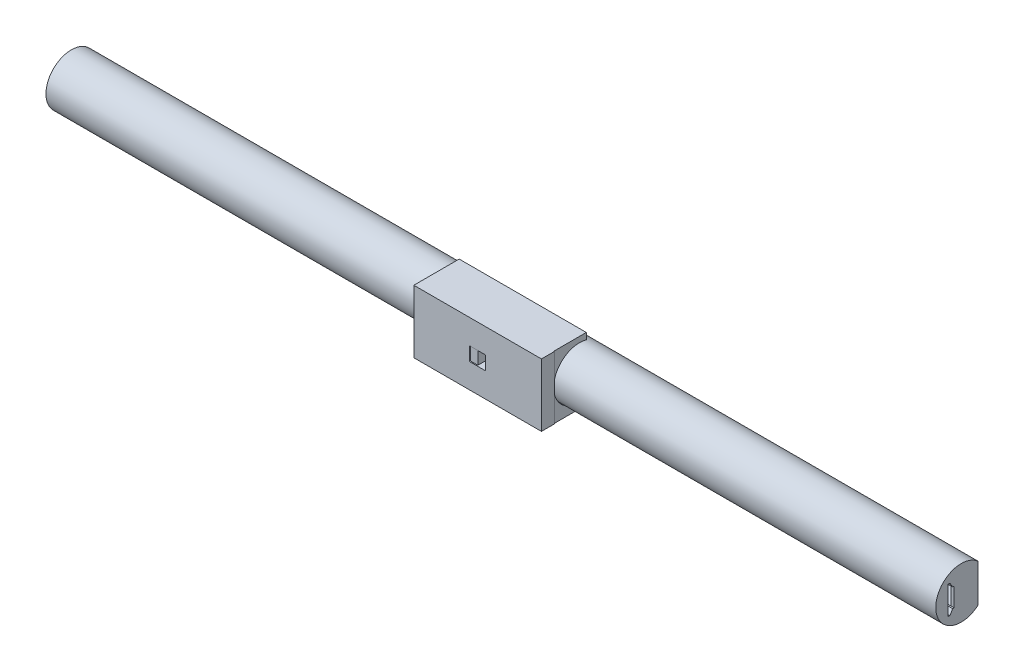
SolidWorks part; units mm, degrees
ref_plane "Front Plane" through (0, 0, 0) normal (0, 0, 1) x (1, 0, 0)
ref_plane "Top Plane" through (0, 0, 0) normal (0, 1, 0) x (1, 0, 0)
ref_plane "Right Plane" through (0, 0, 0) normal (1, 0, 0) x (0, 0, -1)
sketch "NewBarProfile" plane through (0, 0, 0) normal (1, 0, 0) x (0, 1, 0)
  line L0 (7.5, -6.6144) -> (-7.5, -6.6144) construction
  line L1 (-7.5, -6.6144) -> (-6.3, -6.6144)
  line L2 (-6.3, -6.6144) -> (-6.3, 1.2617)
  line L3 (-6.3, 1.2617) -> (0, 4.899) construction
  line L4 (5, 4.899) -> (-5, 4.899) construction
  line L5 (0, -14.4444) -> (0, 14.4444) construction
  line L6 (-5.5, 5.199) -> (5.5, 5.199)
  line L7 (-6.3, 1.2617) -> (-3.7026, 2.7613)
  line L8 (0, 0) -> (-7.1429, 6.9985) construction
  line L9 (-5.5, 4.399) -> (-3.7026, 3.3613)
  line L10 (-5.5, 5.199) -> (-5.5, 4.399)
  line L11 (-3.7026, 3.3613) -> (-3.7026, 2.7613)
  line L12 (7.5, -6.6144) -> (6.3, -6.6144)
  line L13 (3.7026, 3.3613) -> (3.7026, 2.7613)
  line L14 (5.5, 5.199) -> (5.5, 4.399)
  line L15 (5.5, 4.399) -> (3.7026, 3.3613)
  line L16 (6.3, 1.2617) -> (3.7026, 2.7613)
  line L17 (6.3, -6.6144) -> (6.3, 1.2617)
  line L18 (0, -11) -> (0, 11) construction
  circle A0 centre (0, 0) radius 10 construction
  arc A1 (-7.5, -6.6144) -> (7.5, -6.6144) centre (0, 0) cw
  arc A2 (-6.6144, -7.5) -> (-6.6144, 7.5) centre (0, 0) ccw construction
  point P11 (0, 4.899)
  point P14 (0, 0)
  point P17 (-3.2212, 3.0769)
  point P18 (-3.421, 3.3519)
  point P19 (-3.0403, 2.9789)
  point P22 (-3.0403, 2.9789)
  point P30 (5.6596, 5.199)
sketch "Sketch5" plane through (0, 0, 3.7) normal (1, 0, 0) x (0, 1, 0)
  line L0 (0, -16.5814) -> (0, 9.1814) construction
  line L5 (-7.5, -2.6947) -> (-6.4, -4.6) construction
  line L6 (7.5, -2.6947) -> (6.4, -4.6) construction
  line L7 (5.3668, 1) -> (7.5, -2.6947) construction
  line L8 (-5.3668, 1) -> (5.3668, 1) construction
  line L9 (-5.3668, 1) -> (-7.5, -2.6947) construction
  line L10 (7.7309, -2.6947) -> (6.5732, -4.7)
  line L11 (5.4823, 1.2) -> (7.7309, -2.6947)
  line L12 (-5.4823, 1.2) -> (5.4823, 1.2)
  line L13 (-5.4823, 1.2) -> (-7.7309, -2.6947)
  line L14 (-7.7309, -2.6947) -> (-6.5732, -4.7)
  line L15 (-6.5732, -4.7) -> (6.5732, -4.7)
  line L17 (0, -9.7207) -> (0, 9.7207) construction
  line L18 (-6.9, -10.9381) -> (6.9, -10.9381)
  line L19 (0, -10.9381) -> (0, -3.7) construction
  circle A0 centre (0, -3.7) radius 10 construction
  arc A1 (-6.9, -10.9381) -> (6.9, -10.9381) centre (0, -3.7) cw
  point P18 (0, -13.7)
sketch "Sketch8" plane through (0, 0, 3.7) normal (0, -1, 0) x (1, 0, 0)
  line L2 (0, -9.7207) -> (-145, -9.7207)
  line L3 (0, -9.9381) -> (-145, -9.9381)
  line L4 (0, -10.9381) -> (-150, -10.9381)
  point P0 (0, -9.7207)
  point P3 (0, -10.9381)
sketch "Sketch9" plane through (0, 0, 3.7) normal (1, 0, 0) x (0, 1, 0)
  line L0 (-6.9, -10.9381) -> (6.9, -10.9381) construction
  line L3 (-6.9, -10.9381) -> (6.9, -10.9381) construction
  line L4 (-6.4874, -9.9381) -> (6.4874, -9.9381)
  line L5 (-6.4017, -9.7381) -> (6.4017, -9.7381)
  arc A3 (6.9, -10.9381) -> (-6.9, -10.9381) centre (0, -3.7) ccw construction
  arc A4 (6.4874, -9.9381) -> (-6.4874, -9.9381) centre (0, -3.7) ccw
  arc A5 (6.4017, -9.7381) -> (-6.4017, -9.7381) centre (0, -3.7) ccw
sketch "Sketch1" plane through (0, 0, 0) normal (1, 0, 0) x (0, 0, -1)
  line L63 (-5.199, 5.5) -> (-4.399, 5.5)
  line L64 (-4.399, 5.5) -> (-3.3613, 3.7026)
  line L65 (-3.3613, 3.7026) -> (-2.7613, 3.7026)
  line L66 (-2.7613, 3.7026) -> (-1.2617, 6.3)
  line L67 (-1.2617, 6.3) -> (6.6144, 6.3)
  line L68 (6.6144, 6.3) -> (6.6144, 7.5)
  line L69 (6.6144, -7.5) -> (6.6144, -6.3)
  line L70 (6.6144, -6.3) -> (-1.2617, -6.3)
  line L71 (-1.2617, -6.3) -> (-2.7613, -3.7026)
  line L72 (-2.7613, -3.7026) -> (-3.3613, -3.7026)
  line L73 (-3.3613, -3.7026) -> (-4.399, -5.5)
  line L74 (-4.399, -5.5) -> (-5.199, -5.5)
  line L75 (-5.199, -5.5) -> (-5.199, 5.5)
  line L76 (-5.199, 5.5) -> (-4.399, 5.5)
  line L77 (-4.399, 5.5) -> (-3.3613, 3.7026)
  line L78 (-3.3613, 3.7026) -> (-2.7613, 3.7026)
  line L79 (-2.7613, 3.7026) -> (-1.2617, 6.3)
  line L80 (-1.2617, 6.3) -> (6.6144, 6.3)
  line L81 (6.6144, 6.3) -> (6.6144, 7.5)
  line L82 (6.6144, -7.5) -> (6.6144, -6.3)
  line L83 (6.6144, -6.3) -> (-1.2617, -6.3)
  line L84 (-1.2617, -6.3) -> (-2.7613, -3.7026)
  line L85 (-2.7613, -3.7026) -> (-3.3613, -3.7026)
  line L86 (-3.3613, -3.7026) -> (-4.399, -5.5)
  line L87 (-4.399, -5.5) -> (-5.199, -5.5)
  line L88 (-5.199, -5.5) -> (-5.199, 5.5)
  arc A9 (6.6144, 7.5) -> (6.6144, -7.5) centre (0, 0) ccw
  arc A10 (6.6144, 7.5) -> (6.6144, -7.5) centre (0, 0) ccw
  dimension "D1" = 0
extrude "Bar" add sketch "Sketch1" against normal mid plane 350
sketch "Sketch13" plane through (0, 0, -6.6144) normal (0, 0, -1) x (-1, 0, 0)
  line L0 (175, 7.5) -> (175, -7.5)
  line L1 (175, -7.5) -> (173.8, -7.5)
  line L2 (175, -7.5) -> (-175, -7.5) construction
  line L3 (173.8, -7.5) -> (173.8, 7.5)
  line L4 (175, 7.5) -> (-175, 7.5) construction
  line L5 (173.8, 7.5) -> (175, 7.5)
  line L6 (125.4, 7.5) -> (124.6, 7.5)
  line L7 (124.6, 7.5) -> (124.6, -7.5)
  line L8 (124.6, -7.5) -> (125.4, -7.5)
  line L9 (125.4, -7.5) -> (125.4, 7.5)
  line L10 (125, 7.5) -> (125, -7.5) construction
  line L11 (75.4, -7.5) -> (75.4, 7.5)
  line L12 (75.4, 7.5) -> (74.6, 7.5)
  line L13 (74.6, 7.5) -> (74.6, -7.5)
  line L14 (74.6, -7.5) -> (75.4, -7.5)
  line L15 (25.4, -7.5) -> (25.4, 7.5)
  line L16 (25.4, 7.5) -> (24.6, 7.5)
  line L17 (24.6, 7.5) -> (24.6, -7.5)
  line L18 (24.6, -7.5) -> (25.4, -7.5)
  line L19 (-24.6, -7.5) -> (-24.6, 7.5)
  line L20 (-24.6, 7.5) -> (-25.4, 7.5)
  line L21 (-25.4, 7.5) -> (-25.4, -7.5)
  line L22 (-25.4, -7.5) -> (-24.6, -7.5)
  line L23 (-74.6, -7.5) -> (-74.6, 7.5)
  line L24 (-74.6, 7.5) -> (-75.4, 7.5)
  line L25 (-75.4, 7.5) -> (-75.4, -7.5)
  line L26 (-75.4, -7.5) -> (-74.6, -7.5)
  line L27 (-124.6, -7.5) -> (-124.6, 7.5)
  line L28 (-124.6, 7.5) -> (-125.4, 7.5)
  line L29 (-125.4, 7.5) -> (-125.4, -7.5)
  line L30 (-125.4, -7.5) -> (-124.6, -7.5)
  line L31 (0, -34.8434) -> (0, 34.8434) construction
  line L32 (-173.8, -7.5) -> (-173.8, 7.5)
  line L33 (-175, -7.5) -> (-173.8, -7.5)
  line L34 (-175, 7.5) -> (-175, -7.5)
  line L35 (-173.8, 7.5) -> (-175, 7.5)
  point P40 (0, 0)
  dimension "D1" = 1.2
  dimension "D2" = 0.8
  dimension "D3" = 50
  dimension "D5" = 50
  dimension "D4" = 6
extrude "Boss-Extrude1" add sketch "Sketch13" against normal up to vertex (9.3756 mm away) up to point (175, 3.7026, 2.7613)
sketch "Sketch14" plane through (0, 0, 0) normal (0, 1, 0) x (1, 0, 0)
  line L0 (0, 19.6952) -> (0, -19.6952) construction
  line L2 (-175, -10) -> (175, -10) construction
  line L3 (0.1, 6.6144) -> (-0.1, 6.6144)
  line L5 (0.1, 6.6144) -> (0.1, -10)
  line L7 (0.1, -10) -> (-0.1, -10)
  line L8 (-0.1, 6.6144) -> (-0.1, -10)
  line L9 (0.1, 6.6144) -> (-0.1, -10) construction
  line L10 (0.1, -10) -> (-0.1, 6.6144) construction
  line L11 (-175, 6.6144) -> (175, 6.6144) construction
  point P0 (0, -1.6928)
  point P3 (0, 0)
  point P8 (-3.8666, -10)
  point P12 (4.3172, 6.8181)
  point P13 (4.2659, 4.745)
  dimension "D1" = 0.2
extrude "Cut-Extrude1" cut sketch "Sketch14" against normal through all both and the other way through all
sketch "Sketch15" plane through (0, 0, 0) normal (0, 1, 0) x (1, 0, 0)
  line L0 (-0.1, -8) -> (-0.1, -15)
  line L1 (-0.1, -15) -> (-3.1, -15)
  line L2 (-3.1, -15) -> (-10.1, -8)
  line L3 (-10.1, -8) -> (-0.1, -8)
  point P3 (-0.1, -10)
  point P6 (0, 0)
  point P7 (-3.6194, -15)
  point P9 (0, -9.7105)
  dimension "D1" = 2
  dimension "D2" = 5
  dimension "D3" = 45
  dimension "D4" = 3
extrude "Boss-Extrude2" add sketch "Sketch15" along normal mid plane 5
sketch "Sketch16" plane through (-0.1, 0, 0) normal (1, 0, 0) x (0, 0, -1)
  line L48 (2.64, 9.8524) -> (2.64, 12.3524)
  line L49 (2.64, 12.3524) -> (-15.2, 12.3524)
  line L50 (-15.2, 12.3524) -> (-15.2, 2.7)
  line L51 (2.64, 9.8524) -> (8.4798, 8.2877)
  line L52 (-12.3198, 0) -> (12.3198, 0) construction
  line L53 (-15.2, -12.3524) -> (-15.2, -2.7)
  line L54 (2.64, -12.3524) -> (-15.2, -12.3524)
  line L55 (2.64, -9.8524) -> (2.64, -12.3524)
  line L56 (-9.8362, -2.7) -> (-15.2, -2.7)
  line L64 (-9.8362, 2.7) -> (-15.2, 2.7)
  line L65 (-15.2, 2.7) -> (-15.2, -2.7)
  line L66 (-15.2, -2.7) -> (-9.8362, -2.7)
  line L67 (6.8144, -7.5897) -> (6.8144, -6.1)
  line L68 (6.8144, -6.1) -> (-1.1462, -6.1)
  line L69 (-1.1462, -6.1) -> (-2.6458, -3.5026)
  line L70 (-2.6458, -3.5026) -> (-3.4767, -3.5026)
  line L71 (-3.4767, -3.5026) -> (-4.5144, -5.3)
  line L72 (-4.5144, -5.3) -> (-4.999, -5.3)
  line L73 (-4.999, -5.3) -> (-4.999, 5.3)
  line L74 (-4.999, 5.3) -> (-4.5144, 5.3)
  line L75 (-4.5144, 5.3) -> (-3.4767, 3.5026)
  line L76 (-3.4767, 3.5026) -> (-2.6458, 3.5026)
  line L77 (-2.6458, 3.5026) -> (-1.1462, 6.1)
  line L78 (-1.1462, 6.1) -> (6.8144, 6.1)
  line L79 (6.8144, 6.1) -> (6.8144, 7.5897)
  line L80 (-9.8362, 2.7) -> (-15.2, 2.7)
  arc A6 (-9.8362, 2.7) -> (2.64, 9.8524) centre (0, 0) cw
  arc A7 (-9.8362, -2.7) -> (2.64, -9.8524) centre (0, 0) ccw
  arc A8 (6.8144, 7.5897) -> (-9.8362, 2.7) centre (0, 0) ccw
  arc A9 (-9.8362, -2.7) -> (6.8144, -7.5897) centre (0, 0) ccw
  arc A10 (6.8144, 7.5897) -> (-9.8362, 2.7) centre (0, 0) ccw construction
  point P7 (0, 0)
  dimension "D2" = 105
  dimension "D3" = 2.5
  dimension "D1" = 0.2
extrude "Boss-Extrude3" add sketch "Sketch16" along normal mid plane 50 separate body contours A7 L56 L53 L54 L55 | L80 A6 L48 L49 L50 region at (-0.1, 8.6976, 9.0666) region at (-0.1, -8.6976, 9.0666)
sketch "Sketch17" plane through (0, 0, 0) normal (0, 1, 0) x (1, 0, 0)
  line L0 (-25.1, -10.1) -> (-8.2828, -10.1)
  line L2 (-8.2828, -10.1) -> (0, -10.1) construction
  line L4 (-25.1, -15.2) -> (-3.1828, -15.2)
  line L5 (-3.1828, -15.2) -> (-8.2828, -10.1)
  line L7 (0, -19.9979) -> (0, 19.9979) construction
  line L8 (0.1, -15.2) -> (0.1, -7.8)
  line L9 (-3.1828, -15.2) -> (0.1, -15.2)
  line L10 (-10.5828, -7.8) -> (-3.1828, -15.2)
  line L11 (0.1, -7.8) -> (-10.5828, -7.8)
  line L12 (0.1, -15.2) -> (0.1, -7.8) construction
  line L13 (-3.1828, -15.2) -> (0.1, -15.2) construction
  line L14 (-10.5828, -7.8) -> (-3.1828, -15.2) construction
  line L15 (0.1, -7.8) -> (-10.5828, -7.8) construction
  line L16 (-25.1, -9.8362) -> (-25.1, -15.2)
  line L17 (-25.1, -15.2) -> (24.9, -15.2)
  line L18 (24.9, -15.2) -> (24.9, -9.8362)
  line L19 (24.9, -9.8362) -> (-25.1, -9.8362)
  line L20 (-25.1, -10.1) -> (-25.1, -15.2)
  line L24 (8.2828, -10.1) -> (25.1, -10.1)
  line L25 (3.1828, -15.2) -> (8.2828, -10.1)
  line L26 (25.1, -15.2) -> (3.1828, -15.2)
  line L27 (25.1, -10.1) -> (25.1, -15.2)
  circle A0 centre (0, 0) radius 10.1 construction
  point P12 (0, 0)
  point P19 (0, 0)
  dimension "D3" = 20.2
  dimension "D1" = 0.2
  dimension "D2" = 0
extrude "Boss-Extrude4" add sketch "Sketch17" along normal through all and the other way through all
